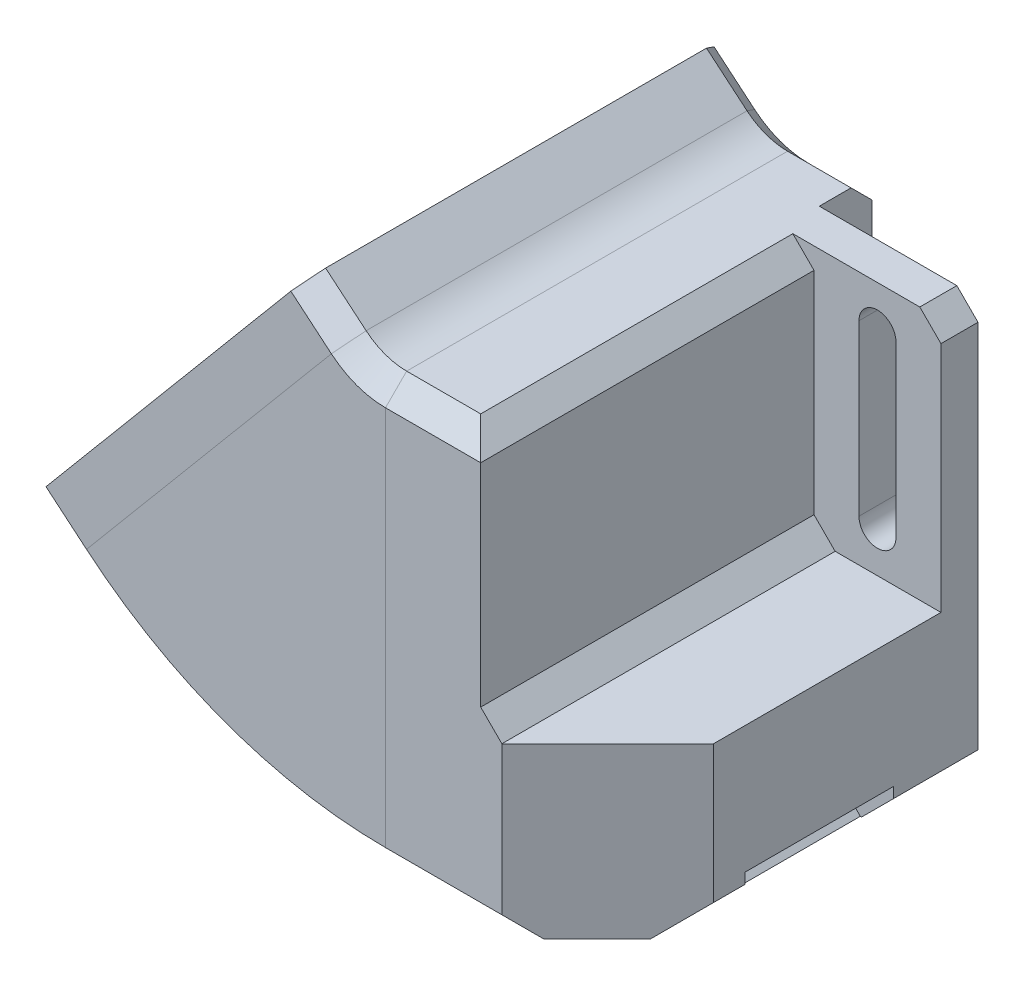
SolidWorks part; units mm, degrees
ref_plane "Front Plane" through (0, 0, 0) normal (0, 0, 1) x (1, 0, 0)
ref_plane "Top Plane" through (0, 0, 0) normal (0, 1, 0) x (1, 0, 0)
ref_plane "Right Plane" through (0, 0, 0) normal (1, 0, 0) x (0, 0, -1)
sketch "Sketch2" plane through (0, 0, 0) normal (0, 0, 1) x (1, 0, 0)
  line L0 (0, 0) -> (-5, 0)
  line L1 (-34.5417, 10.7523) -> (-38.3719, 13.9662)
  line L2 (-38.3719, 13.9662) -> (-12.6604, 44.608) construction
  line L3 (-12.6604, 44.608) -> (-5, 38.1801) construction
  line L4 (-5, 38.1801) -> (0, 38.1801) construction
  line L5 (0, 38.1801) -> (0, 0) construction
  arc A0 (-5, 0) -> (-34.5417, 10.7523) centre (-5, 45.9588) cw
  point P7 (0, 37.61)
  dimension "D1" = 5
  dimension "D2" = 5
  dimension "D3" = 40
  dimension "D4" = 40
  dimension "D5" = 10
sketch "Sketch3" plane through (0, 0, 0) normal (1, 0, 0) x (0, 0, -1)
  line L0 (-17, 37) -> (17, 3) construction
  line L1 (-20, 0) -> (20, 0)
  line L2 (-20, 0) -> (-20, 40)
  line L3 (-20, 40) -> (20, 40)
  line L4 (20, 0) -> (20, 40)
  line L5 (-17, 3) -> (17, 3)
  line L6 (-17, 3) -> (-17, 37)
  line L7 (-17, 37) -> (17, 37)
  line L8 (17, 3) -> (17, 37)
  line L10 (-20, 0) -> (20, 40) construction
  point P8 (0, 20)
  dimension "D1" = 40
  dimension "D2" = 34
sweep "Sweep1" add profiles "Sketch3" path "Sketch2"
sketch "Sketch4" plane through (0, 0, 0) normal (0, 1, 0) x (1, 0, 0)
  line L0 (0, 20) -> (10.583, 8)
  line L1 (10.583, -8) -> (0, -20)
  line L2 (0, -20) -> (0, 20)
  line L3 (10.583, 8) -> (10.583, -8)
  line L4 (10.583, 0) -> (0, 0) construction
  point P8 (0, 0)
  point P10 (0, 0)
  point P11 (0, 0)
  dimension "D1" = 16
  dimension "D2" = 16
sketch "Sketch5" plane through (0, 0, 0) normal (1, 0, 0) x (0, 0, -1)
  line L0 (20, 0) -> (20, 40) construction
  line L1 (-20, 0) -> (20, 0)
  line L2 (-20, 0) -> (-20, 20)
  line L3 (-20, 20) -> (20, 20)
  line L4 (20, 0) -> (20, 20)
  line L5 (17, 37) -> (17, 3) construction
  line L6 (-17, 3) -> (17, 3)
  line L7 (-17, 3) -> (-17, 18)
  line L8 (-17, 18) -> (17, 18)
  line L9 (17, 3) -> (17, 18)
  dimension "D1" = 2
sketch "Sketch7" plane through (0, 0, 0) normal (0, 1, 0) x (1, 0, 0)
  line L1 (0, -20) -> (16, -20)
  line L2 (0, -20) -> (0, 8)
  line L3 (0, 8) -> (16, 8)
  line L4 (16, -20) -> (16, 8)
  dimension "D1" = 8
  dimension "D2" = 16
extrude "Boss-Extrude2" add sketch "Sketch7" along normal up to surface (40 mm away) up to face at (-2.5, 40, 0)
sketch "Sketch8" plane through (0, 0, 0) normal (1, 0, 0) x (0, 0, -1)
  line L1 (20, 0) -> (7, 0)
  line L2 (20, 0) -> (20, 40)
  line L3 (20, 40) -> (7, 40)
  line L4 (7, 0) -> (7, 40)
  point P6 (20, 47.1304)
  point P7 (0, 0)
  dimension "D1" = 13
extrude "Boss-Extrude5" add sketch "Sketch8" against normal blind 5 and the other way blind 1
chamfer "Chamfer1" distance 6 angle 45 1 edges at (-5, 20, -17)
chamfer "Chamfer2" distance 4 angle 45 1 edges at (-5, 20, -7)
sketch "Sketch9" plane through (16, 0, 0) normal (1, 0, 0) x (0, 0, -1)
  line L0 (-20, 0) -> (8, 0) construction
  line L1 (7, 1) -> (-7, 1)
  line L2 (7, 1) -> (7, 4)
  line L3 (7, 4) -> (-7, 4)
  line L4 (-7, 1) -> (-7, 4)
  line L5 (8, 40) -> (8, 0) construction
  line L6 (0, 0) -> (0, 1) construction
  dimension "D1" = 1
  dimension "D2" = 4
  dimension "D3" = 1
extrude "Cut-Extrude1" cut sketch "Sketch9" against normal up to surface (16 mm away) up to face at (0, 20, 5)
sketch "Sketch10" plane through (0, 0, 20) normal (0, 0, 1) x (1, 0, 0)
  line L0 (16, 0) -> (-5, 0) construction
  line L1 (16, 40) -> (4, 40)
  line L2 (16, 40) -> (16, 16)
  line L3 (16, 16) -> (4, 16)
  line L4 (4, 40) -> (4, 16)
  dimension "D1" = 12
  dimension "D2" = 16
extrude "Cut-Extrude2" cut sketch "Sketch10" against normal through all
sketch "Sketch11" plane through (0, 0, -8) normal (0, 0, -1) x (-1, 0, 0)
  line L1 (-1, 40) -> (-16, 40)
  line L2 (-1, 40) -> (-1, 0)
  line L3 (-1, 0) -> (-16, 0)
  line L4 (-16, 40) -> (-16, 0)
extrude "Boss-Extrude6" add sketch "Sketch11" along normal blind 7
sketch "Sketch12" plane through (0, 0, -8) normal (0, 0, 1) x (1, 0, 0)
  line L1 (10, 36) -> (10, 20) construction
  line L2 (11.75, 36) -> (11.75, 20)
  line L3 (8.25, 36) -> (8.25, 20)
  line L4 (16, 40) -> (16, 16) construction
  line L5 (4, 40) -> (16, 40) construction
  line L6 (4, 16) -> (16, 16) construction
  arc A0 (11.75, 36) -> (8.25, 36) centre (10, 36) ccw
  arc A1 (8.25, 20) -> (11.75, 20) centre (10, 20) ccw
  point P2 (10, 28)
  dimension "D1" = 6
  dimension "D2" = 3.5
  dimension "D3" = 4
  dimension "D4" = 4
extrude "Cut-Extrude3" cut sketch "Sketch12" against normal through all
sketch "Sketch13" plane through (0, 40, 0) normal (0, 1, 0) x (1, 0, 0)
  line L0 (16, 15) -> (16, 8) construction
  line L1 (4, 8) -> (16, 8)
  line L2 (4, 8) -> (4, 11.5)
  line L3 (4, 11.5) -> (16, 11.5)
  line L4 (16, 8) -> (16, 11.5)
extrude "Cut-Extrude4" cut sketch "Sketch13" against normal up to surface (24 mm away) up to face at (10, 16, 6)
sketch "Sketch15" plane through (-29.3946, 24.665, 0) normal (-0.766, 0.6428, 0) x (0, 0, 1)
  line L1 (-17, 23.0338) -> (-12.5, 23.0338)
  line L2 (-17, 23.0338) -> (-17, 18.5338)
  line L3 (-17, 18.5338) -> (-12.5, 18.5338)
  line L4 (-12.5, 23.0338) -> (-12.5, 18.5338)
  line L5 (17, 23.0338) -> (12.5, 23.0338)
  line L6 (17, 23.0338) -> (17, 18.5338)
  line L7 (17, 18.5338) -> (12.5, 18.5338)
  line L8 (12.5, 23.0338) -> (12.5, 18.5338)
  line L9 (-17, -10.9662) -> (-12.5, -10.9662)
  line L10 (-17, -10.9662) -> (-17, -6.4662)
  line L11 (-17, -6.4662) -> (-12.5, -6.4662)
  line L12 (-12.5, -10.9662) -> (-12.5, -6.4662)
  line L13 (17, -10.9662) -> (12.5, -10.9662)
  line L14 (17, -10.9662) -> (17, -6.4662)
  line L15 (17, -6.4662) -> (12.5, -6.4662)
  line L16 (12.5, -10.9662) -> (12.5, -6.4662)
  dimension "D1" = 4.5
extrude "Boss-Extrude7" add sketch "Sketch15" against normal blind 5
sketch "Sketch14" plane through (-29.3946, 24.665, 0) normal (-0.766, 0.6428, 0) x (0, 0, 1)
  line L0 (-16, -9.9662) -> (16, 22.0338) construction
  line L1 (-16, 22.0338) -> (16, 22.0338) construction
  line L2 (-16, 22.0338) -> (-16, -9.9662) construction
  line L3 (-16, -9.9662) -> (16, -9.9662) construction
  line L4 (16, 22.0338) -> (16, -9.9662) construction
  line L5 (-20, 26.0338) -> (20, -13.9662) construction
  circle A0 centre (-16, 22.0338) radius 1.5
  circle A1 centre (16, 22.0338) radius 1.5
  circle A2 centre (-16, -9.9662) radius 1.5
  circle A3 centre (16, -9.9662) radius 1.5
  point P10 (0, 6.0338)
  point P11 (0, 0)
  point P14 (-20, 26.0338)
  point P16 (20, -13.9662)
  dimension "D1" = 3
  dimension "D2" = 32
extrude "Cut-Extrude5" cut sketch "Sketch14" against normal blind 8
chamfer "Chamfer3" distance 14 angle 45 1 edges at (0, 4, 0)
chamfer "Chamfer7" distance 3 angle 45 1 edges at (16, 0, 2.5)
chamfer "Chamfer4" distance 14 angle 45 1 edges at (0, 10.5, 7)
chamfer "Chamfer5" distance 2 angle 45 1 edges at (0, 3, 0)
chamfer "Chamfer9" distance 2 angle 45 3 edges at (4, 40, 4.25) (4, 16, 4.25) (16, 40, -13.25)
chamfer "Chamfer10" distance 1.5 angle 90 1 edges at (14, 1, 0) first distance on face at (14.75, 1.75, 1.25)
chamfer "Chamfer11" distance 10 angle 45 1 edges at (16, 9.5, 20)
chamfer "Chamfer12" distance 2 angle 45 16 edges at (-10.7453, 43.0011, -20) (-7.038, 40.3594, -20) (-2, 40, -20) (-36.4568, 12.3593, -20) (-20.7188, 2.7717, -20) (-2, 0, -20) (-36.4568, 12.3593, 20) (-20.7188, 2.7717, 20) (0.5, 0, 20) (-10.7453, 43.0011, 20) (-7.038, 40.3594, 20) (-1.5, 40, 20) (-31.6359, 18.1046, 12.5) (-15.5662, 37.2557, 12.5) (-15.5662, 37.2557, -12.5) (-31.6359, 18.1046, -12.5)
